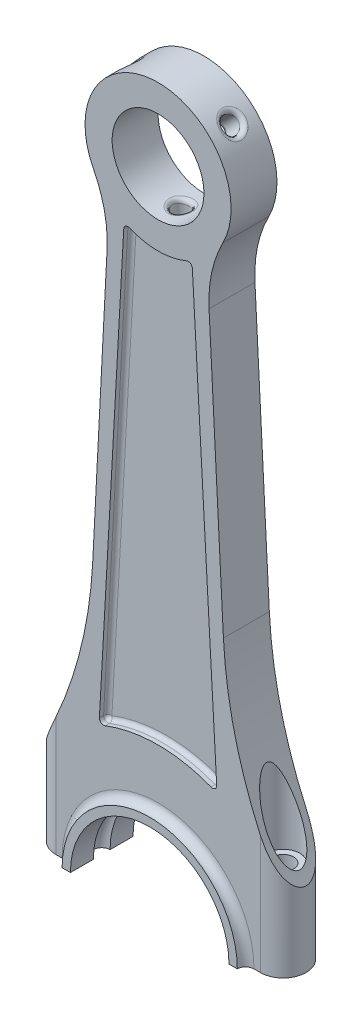
SolidWorks part; units mm, degrees
material "Teak"
ref_plane "Plano frontal" through (0, 0, 0) normal (0, 0, 1) x (1, 0, 0)
ref_plane "Plano superior" through (0, 0, 0) normal (0, 1, 0) x (1, 0, 0)
ref_plane "Plano direito" through (0, 0, 0) normal (1, 0, 0) x (0, 0, -1)
sketch "Sketch1" plane through (0, 0, 0) normal (0, 0, 1) x (1, 0, 0)
  line L0 (-53.8211, 0) -> (53.8211, 0) construction
  line L1 (19, 0) -> (30, 0)
  line L2 (30, 0) -> (30, 18)
  line L3 (0, 0) -> (0, 52.3664) construction
  line L4 (-30, 0) -> (-30, 18)
  line L5 (-19, 0) -> (-30, 0)
  line L6 (12.2232, 131.6153) -> (15.6661, 64.9979)
  line L7 (-12.2232, 131.6153) -> (-15.6661, 64.9979)
  line L8 (30, 0) -> (30, 18)
  line L9 (-30, 0) -> (-30, 18)
  arc A0 (19, 0) -> (-19, 0) centre (0, 0) ccw
  arc A1 (34.9857, 0) -> (-34.9857, 0) centre (0, 0) ccw construction
  circle A2 centre (0, 155) radius 11
  arc A3 (15.5412, 146.9551) -> (-15.5412, 146.9551) centre (0, 155) ccw
  arc A4 (15.6661, 64.9979) -> (30, 18) centre (117.0639, 70.2383) ccw
  arc A5 (12.2232, 131.6153) -> (15.5412, 146.9551) centre (42.1833, 133.1637) cw
  arc A6 (-12.2232, 131.6153) -> (-15.5412, 146.9551) centre (-42.1833, 133.1637) ccw
  arc A7 (-15.6661, 64.9979) -> (-30, 18) centre (-117.0639, 70.2383) cw
  point P4 (0, 0)
  dimension "D1" = 38
  dimension "D4" = 22
  dimension "D6" = 35
  dimension "D7" = 30
  dimension "D2" = 60
  dimension "D3" = 18
  dimension "D5" = 155
extrude "Boss-Extrude1" add sketch "Sketch1" along normal mid plane 11 contours L7 A7 L4 L5 A0 L1 L2 A4 L6 A5 A3 A6 A2 region at (0, 74.0864, 0)
sketch "Sketch2" plane through (0, 0, 5.5) normal (0, 0, 1) x (1, 0, 0)
  line L0 (8.1361, 139.5063) -> (14.145, 32.0144)
  line L1 (0, 155) -> (0, 0) construction
  line L2 (12.2232, 131.6153) -> (15.6661, 64.9979) construction
  line L3 (-8.1361, 139.5063) -> (-14.145, 32.0144)
  arc A0 (-8.1361, 139.5063) -> (8.1361, 139.5063) centre (0, 155) ccw
  arc A1 (14.145, 32.0144) -> (-14.145, 32.0144) centre (0, 0) ccw
  point P10 (13.9447, 98.3066)
  dimension "D1" = 35
  dimension "D2" = 70
  dimension "D3" = 3.5
extrude "Cut-Extrude1" cut sketch "Sketch2" against normal blind 2
sketch "Sketch3" plane through (0, 0, 0) normal (0, -1, 0) x (1, 0, 0)
  line L1 (0, 0) -> (0, 15.7966) construction
  circle A0 centre (24.5, 0) radius 2.5
  circle A1 centre (-24.5, 0) radius 2.5
  dimension "D1" = 5
extrude "Cut-Extrude3" cut sketch "Sketch3" against normal through all
sketch "Sketch4" plane through (0, 0, 0) normal (0, -1, 0) x (1, 0, 0)
  line L0 (0, 0) -> (0, 20.5015) construction
  circle A0 centre (-24.5, 0) radius 4
  circle A1 centre (24.5, 0) radius 4
  dimension "D1" = 8
extrude "Cut-Extrude4" cut sketch "Sketch4" against normal through all from offset 20 offset against normal yes
sketch "Sketch6" plane through (0, 0, 5.5) normal (0, 0, 1) x (1, 0, 0)
  line L0 (-19, 0) -> (-21, 0)
  line L1 (19, 0) -> (21, 0)
  arc A0 (19, 0) -> (-19, 0) centre (0, 0) ccw construction
  arc A1 (19, 0) -> (-19, 0) centre (0, 0) ccw
  arc A2 (21, 0) -> (-21, 0) centre (0, 0) ccw
  dimension "D1" = 42
extrude "Boss-Extrude2" add sketch "Sketch6" along normal blind 2
mirror "Mirror1" about plane through (0, 0, 0) normal (0, 0, 1) of "Boss-Extrude2", "Cut-Extrude1"
fillet "Fillet1" radius 2 2 edges at (0, 21, -5.5) (0, 21, 5.5)
sketch "Sketch7" plane through (0, 0, 0) normal (0, -1, 0) x (1, 0, 0)
  line L0 (-19, 7.5) -> (-19, -7.5) construction
  line L1 (0, 0) -> (0, 23.4082) construction
  circle A0 centre (-19, 0) radius 2
  dimension "D1" = 4
revolve "Cut-Revolve1" cut sketch "Sketch7" angle 360 about L1
sketch "Sketch8" plane through (0, 0, 0) normal (0, -1, 0) x (1, 0, 0)
  circle A0 centre (0, 0) radius 2
  dimension "D1" = 4
extrude "Cut-Extrude5" cut sketch "Sketch8" against normal up to next
sketch "Sketch9" plane through (0, 0, 0) normal (0, 0, 1) x (1, 0, 0)
  line L0 (0, 155) -> (0, 172.5) construction
  line L1 (0, 155) -> (-17.8324, 172.8324) construction
  line L2 (-15.0861, 170.0861) -> (-3.2478, 158.2478)
  line L3 (-15.0861, 170.0861) -> (-13.6719, 171.5003)
  line L4 (-3.2478, 158.2478) -> (-1.8335, 159.662)
  line L5 (-13.6719, 171.5003) -> (-1.8335, 159.662)
  arc A1 (15.5412, 146.9551) -> (-15.5412, 146.9551) centre (0, 155) ccw construction
  dimension "D1" = 45
  dimension "D2" = 2
revolve "Cut-Revolve2" cut sketch "Sketch9" angle 360 about L2
mirror "Mirror2" about plane through (0, 0, 0) normal (1, 0, 0) of "Cut-Revolve2"
fillet "Fillet2" radius 1 5 edges at (10.9186, 168.676, 0.4454) (6.2722, 164.0366, 0.4233) (-10.9186, 168.676, -0.4454) (-6.2722, 164.0366, -0.4233) (-1.9547, 144.1751, -0.4233)
fillet "Fillet3" radius 1 16 edges at (11.1406, 85.7604, 3.5) (0, 35, 3.5) (-11.1406, 85.7604, 3.5) (0, 137.5, 3.5) (-11.1406, 85.7604, -3.5) (0, 35, -3.5) (11.1406, 85.7604, -3.5) (0, 137.5, -3.5) (-14.145, 32.0144, -4.5) (14.145, 32.0144, -4.5) (8.1361, 139.5063, -4.5) (-8.1361, 139.5063, -4.5) (-8.1361, 139.5063, 4.5) (8.1361, 139.5063, 4.5) (-14.145, 32.0144, 4.5) (14.145, 32.0144, 4.5)
fillet "Fillet4" 2 edges at (-30, 9, -5.5) (-30, 9, 5.5) type full round first side face at (0, 64.1969, -5.5) second side face at (0, 64.1969, 5.5) middle face at (-30, 9, 0)
fillet "Fillet5" 2 edges at (30, 9, -5.5) (30, 9, 5.5) type full round first side face at (0.8179, 65.1121, -5.5) second side face at (0.8179, 65.1121, 5.5) middle face at (30, 9, 0)
